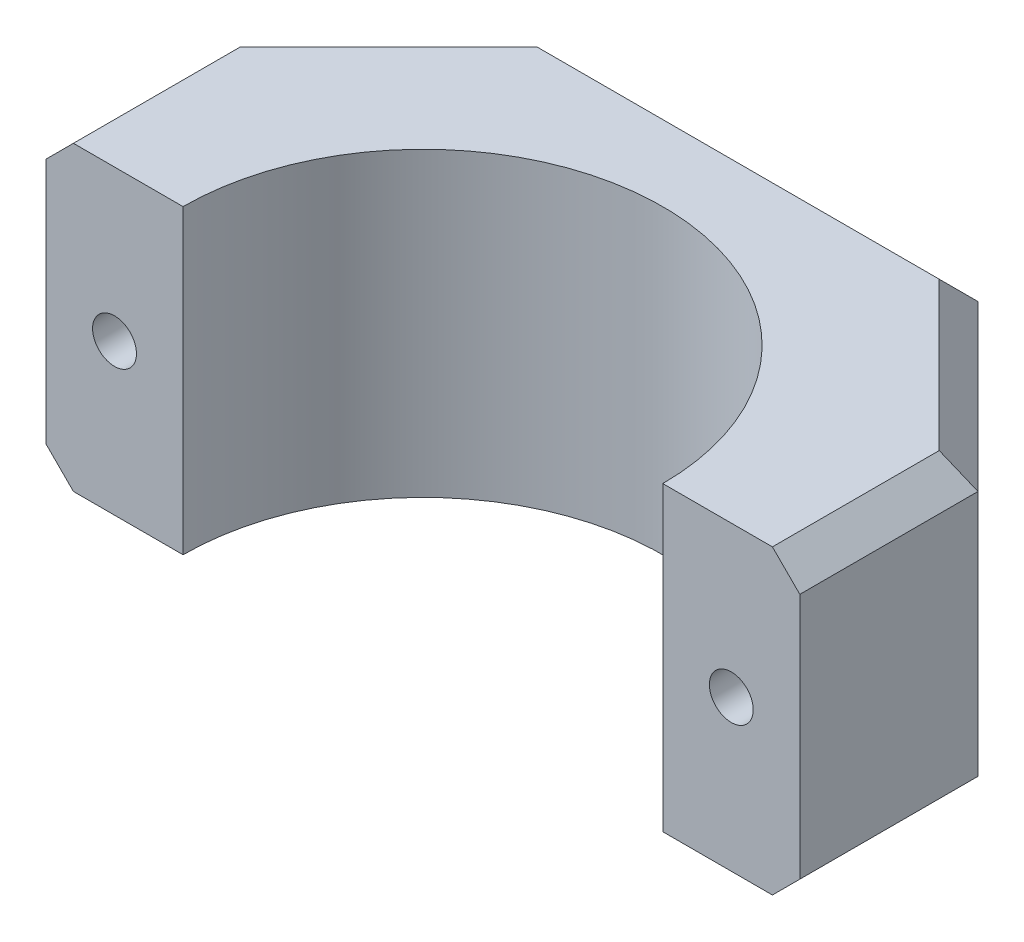
SolidWorks part; units mm, degrees
ref_plane "Front Plane" through (0, 0, 0) normal (0, 0, 1) x (1, 0, 0)
ref_plane "Top Plane" through (0, 0, 0) normal (0, 1, 0) x (1, 0, 0)
ref_plane "Right Plane" through (0, 0, 0) normal (1, 0, 0) x (0, 0, -1)
sketch "Sketch1" plane through (0, 0, 0) normal (0, 1, 0) x (1, 0, 0)
  line L0 (-38.9855, -2.0289) -> (-48.9855, -2.0289)
  line L1 (-48.9855, -2.0289) -> (-48.9855, 22.9711)
  line L2 (-48.9855, 22.9711) -> (6.0145, 22.9711)
  line L3 (6.0145, 22.9711) -> (6.0145, -2.0289)
  line L4 (6.0145, -2.0289) -> (-3.9855, -2.0289)
  arc A0 (-38.9855, -2.0289) -> (-3.9855, -2.0289) centre (-21.4855, -2.0289) cw
  dimension "D1" = 17.5
  dimension "D2" = 10
  dimension "D3" = 25
extrude "Boss-Extrude1" add sketch "Sketch1" along normal blind 22
chamfer "Chamfer1" distance 12 distance2 12 2 edges at (6.0145, 11, -22.9711) (-48.9855, 11, -22.9711)
sketch "Sketch2" plane through (0, 0, -22.9711) normal (0, 0, -1) x (-1, 0, 0)
  line L0 (48.9855, 22) -> (48.9855, 0) construction
  line L1 (-6.0145, 22) -> (-6.0145, 0) construction
  line L2 (5.9855, 0) -> (36.9855, 0) construction
  circle A0 centre (-1.0145, 11) radius 1.6
  circle A1 centre (43.9855, 11) radius 1.6
  circle A2 centre (43.9855, 11) radius 3
  circle A3 centre (-1.0145, 11) radius 3
  point P8 (-6.0145, 11)
  dimension "D4" = 3.2
  dimension "D5" = 6
  dimension "D1" = 5
  dimension "D2" = 5
  dimension "D3" = 11
extrude "Cut-Extrude1" cut sketch "Sketch2" against normal up to surface (25 mm away) contours A1 | A0 region at (1.0145, 11, -22.9711) region at (-43.9855, 11, -22.9711) up to face at (-43.9855, 11, 2.0289)
extrude "Cut-Extrude2" cut sketch "Sketch2<4>" against normal offset from surface (21 mm away) 4 up to face at (-45.5855, 11, 2.0289)
sketch "Sketch2<4>" plane through (0, 0, -22.9711) normal (0, 0, -1) x (-1, 0, 0) same geometry as "Sketch2"
chamfer "Chamfer2" distance 2 angle 45 10 edges at (-48.9855, 0, -4.4711) (-42.9855, 0, -16.9711) (6.0145, 0, -4.4711) (-21.4855, 0, -22.9711) (0.0145, 0, -16.9711) (6.0145, 22, -4.4711) (-48.9855, 22, -4.4711) (-42.9855, 22, -16.9711) (-21.4855, 22, -22.9711) (0.0145, 22, -16.9711)
